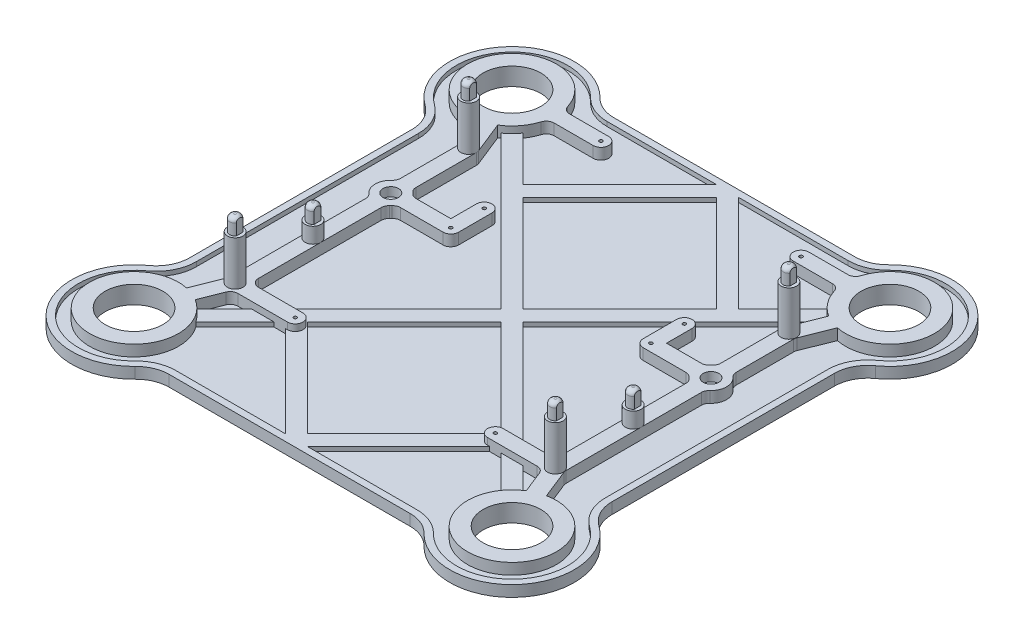
SolidWorks part; units mm, degrees
material "ABS"
ref_plane "Front Plane" through (0, 0, 0) normal (0, 0, 1) x (1, 0, 0)
ref_plane "Top Plane" through (0, 0, 0) normal (0, 1, 0) x (1, 0, 0)
ref_plane "Right Plane" through (0, 0, 0) normal (1, 0, 0) x (0, 0, -1)
sketch "Sketch1" plane through (0, 0, 0) normal (0, 1, 0) x (1, 0, 0)
  line L2 (-270.4419, 0) -> (243.27, 0) construction
  line L3 (-55, 0) -> (55, 0) construction
  line L4 (0, 100) -> (54.1942, 100)
  line L5 (95, -50.0143) -> (95, 50.0143)
  line L6 (0, -100) -> (0, 100)
  line L7 (0, -100) -> (54.1942, -100)
  circle A0 centre (85, 85) radius 13
  circle A1 centre (85, 85) radius 80 construction
  arc A2 (101.2791, 62.2186) -> (64.9404, 104.5349) centre (85, 85) ccw
  arc A3 (54.1942, 100) -> (64.9404, 104.5349) centre (54.1942, 115) ccw
  arc A4 (95, 50.0143) -> (101.2791, 62.2186) centre (110, 50.0143) cw
  arc A15 (95, -50.0143) -> (101.2791, -62.2186) centre (110, -50.0143) ccw
  arc A16 (54.1942, -100) -> (64.9404, -104.5349) centre (54.1942, -115) cw
  arc A17 (101.2791, -62.2186) -> (64.9404, -104.5349) centre (85, -85) cw
  circle A18 centre (85, -85) radius 80 construction
  circle A19 centre (85, -85) radius 13
  dimension "D1" = 26
  dimension "D2" = 10
  dimension "D3" = 200
  dimension "D4" = 160
extrude "Base" add sketch "Sketch1" along normal blind 3
sketch "Sketch2" plane through (0, 3, 0) normal (0, 1, 0) x (1, 0, 0)
  line L2 (95, 0) -> (0, 0) construction
  line L4 (0, 100) -> (0, -100)
  line L8 (54.1942, 100) -> (0, 100)
  line L10 (0, -100) -> (54.1942, -100)
  line L11 (95, -50.0143) -> (95, 50.0143)
  line L12 (54.1942, 100) -> (0, 100)
  line L14 (0, -100) -> (54.1942, -100)
  line L15 (95, -50.0143) -> (95, 50.0143)
  arc A24 (54.1942, 100) -> (64.9404, 104.5349) centre (54.1942, 115) ccw
  arc A31 (64.9404, -104.5349) -> (54.1942, -100) centre (54.1942, -115) ccw
  arc A32 (64.9404, -104.5349) -> (101.2791, -62.2186) centre (85, -85) ccw
  arc A33 (95, -50.0143) -> (101.2791, -62.2186) centre (110, -50.0143) ccw
  arc A34 (101.2791, 62.2186) -> (95, 50.0143) centre (110, 50.0143) ccw
  arc A35 (101.2791, 62.2186) -> (64.9404, 104.5349) centre (85, 85) ccw
  arc A36 (54.1942, 100) -> (64.9404, 104.5349) centre (54.1942, 115) ccw
  arc A43 (64.9404, -104.5349) -> (54.1942, -100) centre (54.1942, -115) ccw
  arc A44 (64.9404, -104.5349) -> (101.2791, -62.2186) centre (85, -85) ccw
  arc A45 (95, -50.0143) -> (101.2791, -62.2186) centre (110, -50.0143) ccw
  arc A46 (101.2791, 62.2186) -> (95, 50.0143) centre (110, 50.0143) ccw
  arc A47 (101.2791, 62.2186) -> (64.9404, 104.5349) centre (85, 85) ccw
  dimension "D1" = 0
extrude "thin rim" add sketch "Sketch2" along normal blind 2 thin thin type one direction reverse wall 3
sketch "Sketch4" plane through (0, 0, 0) normal (0, -1, 0) x (1, 0, 0)
  circle A2 centre (85, 85) radius 13 construction
  circle A3 centre (85, -85) radius 13 construction
  circle A6 centre (85, 85) radius 13
  circle A7 centre (85, -85) radius 13
extrude "wheel mount" add sketch "Sketch4" against normal blind 8 thin thin type one direction wall 7
sketch "Sketch5" plane through (0, 3, 0) normal (0, 1, 0) x (1, 0, 0)
  circle A0 centre (72.0096, -17.5) radius 17.5
  circle A1 centre (72.0096, 17.5) radius 17.5
  circle A2 centre (72.0096, 52.5) radius 17.5
  circle A3 centre (72.0096, -52.5) radius 17.5
  circle A4 centre (85, -85) radius 17.5
  circle A5 centre (85, 85) radius 17.5
  circle A8 centre (72.0096, -52.5) radius 3.5
  circle A9 centre (72.0096, -17.5) radius 3.5
  circle A10 centre (72.0096, 52.5) radius 3.5
  circle A11 centre (85, -85) radius 20 construction
  circle A12 centre (85, 85) radius 20 construction
  dimension "D1" = 35
  dimension "D2" = 7
  dimension "D3" = 35
extrude "upper base mount" add sketch "Sketch5" along normal blind 25 separate body contours A10 | A8
sketch "Sketch11" plane through (0, 3, 0) normal (0, 1, 0) x (1, 0, 0)
  line L0 (85, 85) -> (72.0096, 52.5) construction
  line L1 (72.0096, 52.5) -> (72.0096, -52.5) construction
  line L2 (72.0096, -52.5) -> (85, -85) construction
  line L3 (74.4415, 68.0142) -> (68.5096, 53.1736)
  line L4 (68.5096, -49) -> (45, -49)
  line L5 (69.6394, -56) -> (74.4415, -68.0142)
  line L6 (80.9415, 65.4161) -> (75.5096, 51.8264)
  line L7 (75.5096, 51.8264) -> (75.5096, 23.5622)
  line L8 (75.5096, -51.8264) -> (80.9415, -65.4161)
  line L9 (75.5096, 11.4378) -> (75.5096, -51.8264)
  line L10 (68.5096, 11.4378) -> (68.5096, -49)
  line L11 (118.5078, 0) -> (0, 0) construction
  line L12 (69.6394, -56) -> (45, -56)
  line L13 (65.0096, 17.5) -> (41.5, 17.5) construction
  line L14 (65.9474, 21) -> (48.5, 21)
  line L15 (65.9474, 14) -> (45, 14)
  line L16 (68.5096, 53.1736) -> (68.5096, 23.5622)
  line L17 (85, 85) -> (45, 85) construction
  line L18 (48.5, 21) -> (48.5, 32.5)
  line L19 (41.5, 17.5) -> (41.5, 32.5)
  line L20 (0, -4.4) -> (0, 4.4) construction
  line L21 (65.3086, 88.5) -> (45, 88.5)
  line L22 (65.3086, 81.5) -> (45, 81.5)
  line L23 (65.3086, 81.5) -> (65.3086, 88.5)
  circle A0 centre (85, 85) radius 20 construction
  arc A1 (45, 88.5) -> (45, 81.5) centre (45, 85) ccw
  arc A2 (74.4415, -68.0142) -> (80.9415, -65.4161) centre (85, -85) cw
  arc A3 (74.4415, 68.0142) -> (80.9415, 65.4161) centre (85, 85) ccw
  arc A4 (68.5096, 23.5622) -> (65.9474, 21) centre (72.0096, 17.5) ccw
  arc A5 (75.5096, 11.4378) -> (75.5096, 23.5622) centre (72.0096, 17.5) ccw
  arc A6 (45, -49) -> (45, -56) centre (45, -52.5) ccw
  arc A7 (41.5, 32.5) -> (48.5, 32.5) centre (45, 32.5) cw
  circle A8 centre (85, -85) radius 20 construction
  arc A9 (65.9474, 14) -> (68.5096, 11.4378) centre (72.0096, 17.5) ccw
  arc A10 (45, 14) -> (41.5, 17.5) centre (45, 17.5) cw
  point P44 (41.5, 14)
  dimension "D1" = 7
  dimension "D2" = 3.5
  dimension "D4" = 7
  dimension "D7" = 3.5
  dimension "D3" = 3.5
  dimension "D5" = 70
  dimension "D6" = 45
  dimension "D8" = 3.5
  dimension "D9" = 3.5
  dimension "D10" = 15
extrude "gear rim" add sketch "Sketch11" along normal up to surface (5 mm away) up to face at (85, 8, 72)
extrude "gear mount" add sketch "Sketch5<3>" along normal blind 12 contours A9
sketch "Sketch5<3>" plane through (0, 3, 0) normal (0, 1, 0) x (1, 0, 0) same geometry as "Sketch5"
sketch "Sketch12" plane through (0, 8, 0) normal (0, 1, 0) x (1, 0, 0)
  circle A0 centre (72.0096, 17.5) radius 3.5
  circle A1 centre (72.0096, -17.5) radius 3.5 construction
extrude "servo gear mount" cut sketch "Sketch12" against normal blind 4
fillet "gear rim fillet" radius 3.5 13 edges at (75.5096, 5.5, -51.8264) (75.5096, 5.5, -23.5622) (75.5096, 5.5, -11.4378) (75.5096, 5.5, 51.8264) (68.5096, 5.5, -23.5622) (69.6394, 5.5, 56) (68.5096, 5.5, 49) (68.5096, 5.5, -11.4378) (65.9474, 5.5, -14) (65.9474, 5.5, -21) (68.5096, 5.5, -53.1736) (65.3086, 5.5, -88.5) (65.3086, 5.5, -81.5)
sketch "Sketch13" plane through (0, 28, 0) normal (0, 1, 0) x (1, 0, 0)
  line L0 (74.0096, 54) -> (74.0096, 51)
  line L2 (70.0096, 54) -> (70.0096, 51)
  line L5 (74.0096, -51) -> (74.0096, -54)
  line L7 (70.0096, -54) -> (70.0096, -51)
  arc A0 (70.0096, 51) -> (74.0096, 51) centre (72.0096, 52.5) ccw
  arc A2 (74.0096, -51) -> (70.0096, -51) centre (72.0096, -52.5) ccw
  arc A3 (74.0096, 54) -> (70.0096, 54) centre (72.0096, 52.5) ccw
  arc A5 (70.0096, -54) -> (74.0096, -54) centre (72.0096, -52.5) ccw
  dimension "D1" = 5
  dimension "D2" = 2
  dimension "D3" = 2
extrude "upper base fixers" add sketch "Sketch13" along normal blind 7
sketch "Sketch14" plane through (0, 15, 0) normal (0, 1, 0) x (1, 0, 0)
  line L0 (70.0096, -51) -> (70.0096, -54) construction
  line L1 (74.0096, -54) -> (74.0096, -51) construction
  line L2 (74.0096, -19) -> (74.0096, -16)
  line L3 (70.0096, -16) -> (70.0096, -19)
  circle A0 centre (72.0096, -17.5) radius 3.5 construction
  arc A2 (70.0096, -54) -> (74.0096, -54) centre (72.0096, -52.5) ccw construction
  arc A3 (74.0096, -51) -> (70.0096, -51) centre (72.0096, -52.5) ccw construction
  arc A4 (70.0096, -19) -> (74.0096, -19) centre (72.0096, -17.5) ccw
  arc A5 (74.0096, -16) -> (70.0096, -16) centre (72.0096, -17.5) ccw
extrude "gear fixer" add sketch "Sketch14" along normal blind 7
fillet "fixer fillet" radius 2 3 edges at (72.0096, 35, -55) (72.0096, 22, 20) (72.0096, 35, 50)
sketch "Sketch22" plane through (0, 3, 0) normal (0, 1, 0) x (1, 0, 0)
  line L0 (0, 0) -> (85, -85) construction
  line L1 (68.6012, -73.551) -> (48.5, -53.4497)
  line L2 (0, -4.4) -> (0, 4.4) construction
  line L3 (4.9497, 0) -> (73.551, -68.6012)
  line L4 (20.746, 0) -> (-16.4989, 0) construction
  line L5 (68.6012, 73.551) -> (48.5, 53.4497)
  line L6 (4.9497, 0) -> (73.551, 68.6012)
  line L7 (0, 4.9497) -> (0, -4.9497)
  line L8 (68.6012, -73.551) -> (73.551, -68.6012)
  line L9 (73.551, 68.6012) -> (68.6012, 73.551)
  line L10 (46.0251, -50.9749) -> (0, -97) construction
  line L11 (48.5, -53.4497) -> (4.9497, -97)
  line L12 (0, -97) -> (54.1942, -97) construction
  line L13 (43.5503, -48.5) -> (0, -92.0503)
  line L14 (0, 97) -> (0, -97) construction
  line L15 (43.5503, -48.5) -> (0, -4.9497)
  line L16 (48.5, 53.4497) -> (4.9497, 97)
  line L17 (43.5503, 48.5) -> (0, 92.0503)
  line L18 (43.5503, 48.5) -> (0, 4.9497)
  line L19 (0, 92.0503) -> (0, 97)
  line L20 (0, 97) -> (4.9497, 97)
  line L21 (0, -92.0503) -> (0, -97)
  line L22 (0, -97) -> (4.9497, -97)
  circle A0 centre (85, -85) radius 20 construction
  dimension "D1" = 3.5
  dimension "D2" = 3.5
  dimension "D3" = 3.5
  dimension "D4" = 3.5
extrude "Boss-Extrude1" add sketch "Sketch22" along normal blind 2
sketch "Sketch23" plane through (0, 8, 0) normal (0, 1, 0) x (1, 0, 0)
  circle A0 centre (45, -52.5) radius 0.75
  circle A1 centre (45, 17.5) radius 0.75
  circle A2 centre (45, 32.5) radius 0.75
  circle A3 centre (45, 85) radius 0.75
  dimension "D1" = 1.5
extrude "Cut-Extrude1" cut sketch "Sketch23" against normal through all
mirror "Mirror1" about plane through (0, 0, 0) normal (1, 0, 0) of "Cut-Extrude1", "Boss-Extrude1", "fixer fillet", "gear fixer", "upper base fixers", "gear rim fillet", "servo gear mount", "gear mount", "gear rim", "upper base mount", "wheel mount", "thin rim", "Base"
